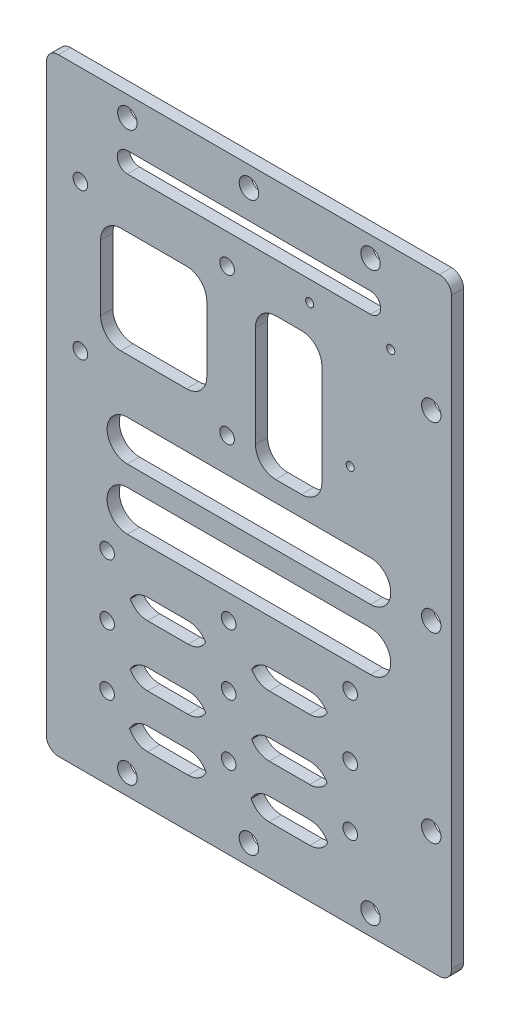
SolidWorks part; units mm, degrees
ref_plane "Plan de face" through (0, 0, 0) normal (0, 0, 1) x (1, 0, 0)
ref_plane "Plan de dessus" through (0, 0, 0) normal (0, 1, 0) x (1, 0, 0)
ref_plane "Plan de droite" through (0, 0, 0) normal (1, 0, 0) x (0, 0, -1)
sketch "Esquisse1" plane through (0, 0, 0) normal (0, 0, 1) x (1, 0, 0)
  line L0 (0, 0) -> (0, 150)
  line L1 (0, 0) -> (100, 0)
  line L2 (0, 150) -> (100, 150)
  line L3 (100, 0) -> (100, 150)
  dimension "D1" = 100
  dimension "D2" = 150
extrude "Boss.-Extru.1" add sketch "Esquisse1" along normal blind 3
sketch "Esquisse3" plane through (0, 0, 3) normal (0, 0, 1) x (1, 0, 0)
  line L0 (0, 0) -> (100, 0) construction
  line L1 (100, 0) -> (100, 150) construction
  line L2 (100, 150) -> (0, 150) construction
  line L3 (0, 150) -> (0, 0) construction
  line L4 (100, 75) -> (0, 75) construction
  line L5 (50, 150) -> (50, 0) construction
  circle A0 centre (20, 145) radius 2.4
  circle A1 centre (50, 145) radius 2.4
  circle A2 centre (80, 145) radius 2.4
  circle A3 centre (95, 120) radius 2.4
  circle A4 centre (95, 75) radius 2.4
  circle A5 centre (95, 30) radius 2.4
  circle A6 centre (80, 5) radius 2.4
  circle A7 centre (50, 5) radius 2.4
  circle A8 centre (20, 5) radius 2.4
  dimension "D1" = 4.8
  dimension "D2" = 4.8
  dimension "D3" = 4.8
  dimension "D4" = 4.8
  dimension "D5" = 4.8
  dimension "D6" = 4.8
  dimension "D7" = 4.8
  dimension "D8" = 4.8
  dimension "D9" = 4.8
  dimension "D12" = 5
  dimension "D15" = 5
  dimension "D16" = 5
  dimension "D17" = 5
  dimension "D18" = 5
  dimension "D26" = 30
  dimension "D27" = 30
  dimension "D10" = 5
  dimension "D11" = 5
  dimension "D13" = 5
  dimension "D14" = 5
  dimension "D20" = 30
  dimension "D21" = 30
  dimension "D22" = 30
  dimension "D23" = 30
extrude "Enlèv. mat.-Extru.2" cut sketch "Esquisse3" against normal blind 3
sketch "Esquisse4" plane through (0, 0, 3) normal (0, 0, 1) x (1, 0, 0)
  line L0 (100, 0) -> (100, 150) construction
  line L1 (0, 50) -> (100, 50) construction
  line L2 (5, 129) -> (5, 86) construction
  line L3 (5, 86) -> (48, 86) construction
  line L4 (48, 86) -> (48, 129) construction
  line L5 (48, 129) -> (5, 129) construction
  line L6 (0, 150) -> (0, 0) construction
  line L7 (100, 150) -> (0, 150) construction
  line L8 (8.4, 125.6) -> (44.6, 125.6) construction
  line L9 (44.6, 125.6) -> (44.6, 89.4) construction
  line L10 (8.4, 89.4) -> (8.4, 125.6) construction
  line L11 (8.4, 89.4) -> (44.6, 89.4) construction
  line L12 (26.5, 129) -> (26.5, 125.6) construction
  line L13 (8.4, 107.5) -> (5, 107.5) construction
  line L14 (80, 76) -> (20, 76) construction
  line L15 (80, 71) -> (20, 71)
  line L16 (80, 81) -> (20, 81)
  line L17 (100, 10) -> (0, 10) construction
  line L18 (0, 10) -> (100, 10) construction
  line L19 (100, 10) -> (90, 0) construction
  line L20 (0, 0) -> (100, 0) construction
  line L21 (90, 0) -> (90, 150) construction
  line L22 (90, 150) -> (100, 140) construction
  line L23 (100, 140) -> (-1.2496, 140) construction
  line L24 (15, 50) -> (15, 20) construction
  line L25 (0, 35) -> (100, 35) construction
  line L26 (20, 45) -> (20, 40)
  line L27 (0, 20) -> (100, 20) construction
  line L28 (45, 50) -> (45, 20) construction
  line L29 (20, 45) -> (40, 45)
  line L30 (75, 50) -> (75, 20) construction
  line L31 (20, 40) -> (40, 40)
  line L32 (40, 45) -> (40, 40)
  line L33 (50, 45) -> (50, 40)
  line L34 (50, 45) -> (70, 45)
  line L35 (50, 40) -> (70, 40)
  line L36 (70, 45) -> (70, 40)
  line L37 (50, 30) -> (50, 25)
  line L38 (50, 30) -> (70, 30)
  line L39 (50, 25) -> (70, 25)
  line L40 (70, 30) -> (70, 25)
  line L41 (20, 30) -> (20, 25)
  line L42 (20, 30) -> (40, 30)
  line L43 (20, 25) -> (40, 25)
  line L44 (40, 30) -> (40, 25)
  line L45 (13.4, 120.6) -> (13.4, 94.4)
  line L46 (13.4, 120.6) -> (39.6, 120.6)
  line L47 (13.4, 94.4) -> (39.6, 94.4)
  line L48 (39.6, 120.6) -> (39.6, 94.4)
  line L49 (51.6, 121) -> (68, 121)
  line L50 (51.6, 121) -> (51.6, 86)
  line L51 (68, 121) -> (68, 86)
  line L52 (51.6, 86) -> (68, 86)
  line L53 (20, 17.5) -> (20, 12)
  line L54 (20, 17.5) -> (40, 17.5)
  line L55 (20, 12) -> (40, 12)
  line L56 (40, 17.5) -> (40, 12)
  line L57 (50, 17.5) -> (50, 12)
  line L58 (50, 17.5) -> (70, 17.5)
  line L59 (50, 12) -> (70, 12)
  line L60 (70, 17.5) -> (70, 12)
  line L61 (20, 61) -> (80, 61) construction
  line L62 (20, 66) -> (80, 66)
  line L63 (20, 56) -> (80, 56)
  line L64 (20, 135.5) -> (80, 135.5) construction
  line L65 (20, 138) -> (80, 138)
  line L66 (20, 133) -> (80, 133)
  circle A1 centre (44.6, 89.4) radius 1.8
  circle A4 centre (8.4, 125.6) radius 1.8
  circle A5 centre (44.6, 125.6) radius 1.8
  circle A6 centre (85, 128) radius 1
  circle A7 centre (65, 128) radius 1
  circle A8 centre (75, 98) radius 1
  circle A11 centre (8.4, 89.4) radius 1.8
  arc A13 (80, 71) -> (80, 81) centre (80, 76) ccw
  arc A14 (20, 81) -> (20, 71) centre (20, 76) ccw
  circle A15 centre (15, 50) radius 1.8
  circle A16 centre (45, 35) radius 1.8
  circle A17 centre (15, 20) radius 1.8
  circle A18 centre (45, 50) radius 1.8
  circle A19 centre (15, 35) radius 1.8
  circle A20 centre (45, 20) radius 1.8
  circle A21 centre (75, 20) radius 1.8
  circle A22 centre (75, 35) radius 1.8
  circle A23 centre (75, 50) radius 1.8
  arc A24 (20, 66) -> (20, 56) centre (20, 61) ccw
  arc A25 (80, 56) -> (80, 66) centre (80, 61) ccw
  arc A26 (20, 138) -> (20, 133) centre (20, 135.5) ccw
  arc A27 (80, 133) -> (80, 138) centre (80, 135.5) ccw
  circle A28 centre (20, 5) radius 2.4 construction
  circle A29 centre (50, 5) radius 2.4 construction
  point P4 (50, 76)
  point P103 (50, 61)
  point P108 (50, 135.5)
  dimension "D6" = 3.6
  dimension "D7" = 3.6
  dimension "D8" = 3.6
  dimension "D9" = 3.6
  dimension "D10" = 20
  dimension "D11" = 5
  dimension "D19" = 2
  dimension "D20" = 2
  dimension "D21" = 2
  dimension "D22" = 10
  dimension "D23" = 10
  dimension "D25" = 3.6
  dimension "D4" = 10
  dimension "D5" = 20
  dimension "D12" = 43
  dimension "D13" = 43
  dimension "D14" = 21
  dimension "D15" = 5
  dimension "D16" = 36.2
  dimension "D17" = 10
  dimension "D18" = 36.2
  dimension "D24" = 10
  dimension "D26" = 15
  dimension "D27" = 15
  dimension "D28" = 30
  dimension "D29" = 30
  dimension "D30" = 15
  dimension "D31" = 20
  dimension "D32" = 30
  dimension "D33" = 30
  dimension "D34" = 10
  dimension "D35" = 22
  dimension "D36" = 15
  dimension "D37" = 20
  dimension "D38" = 5
  dimension "D39" = 5
  dimension "D40" = 5
  dimension "D41" = 20
  dimension "D42" = 5
  dimension "D43" = 5
  dimension "D44" = 5
  dimension "D45" = 5
  dimension "D46" = 5
  dimension "D47" = 5
  dimension "D48" = 5
  dimension "D49" = 5
  dimension "D50" = 5
  dimension "D51" = 5
  dimension "D52" = 5
  dimension "D53" = 5
  dimension "D54" = 5
  dimension "D55" = 5
  dimension "D56" = 5
  dimension "D57" = 5
  dimension "D58" = 7
  dimension "D59" = 10
  dimension "D60" = 5
  dimension "D61" = 5
  dimension "D62" = 5
  dimension "D63" = 2.5
  dimension "D64" = 7
  dimension "D65" = 10
  dimension "D66" = 5
  dimension "D67" = 20
  dimension "D68" = 20
  dimension "D69" = 7
  dimension "D70" = 5
  dimension "D71" = 7
  dimension "D72" = 7
  dimension "D73" = 5
  dimension "D74" = 5
  dimension "D75" = 20
  dimension "D76" = 20
extrude "Enlèv. mat.-Extru.3" cut sketch "Esquisse4" against normal blind 10
fillet "Congé1" radius 5 32 edges at (50, 25, 1.5) (50, 45, 1.5) (40, 45, 1.5) (40, 25, 1.5) (20, 25, 1.5) (20, 45, 1.5) (13.4, 94.4, 1.5) (39.6, 94.4, 1.5) (39.6, 120.6, 1.5) (13.4, 120.6, 1.5) (70, 40, 1.5) (70, 45, 1.5) (50, 40, 1.5) (50, 30, 1.5) (70, 30, 1.5) (70, 25, 1.5) (40, 40, 1.5) (40, 30, 1.5) (20, 30, 1.5) (20, 40, 1.5) (20, 12, 1.5) (20, 17.5, 1.5) (40, 12, 1.5) (40, 17.5, 1.5) (50, 12, 1.5) (50, 17.5, 1.5) (70, 12, 1.5) (70, 17.5, 1.5) (51.6, 86, 1.5) (68, 86, 1.5) (68, 121, 1.5) (51.6, 121, 1.5)
fillet "Congé2" radius 3 4 edges at (100, 150, 1.5) (0, 150, 1.5) (0, 0, 1.5) (100, 0, 1.5)
